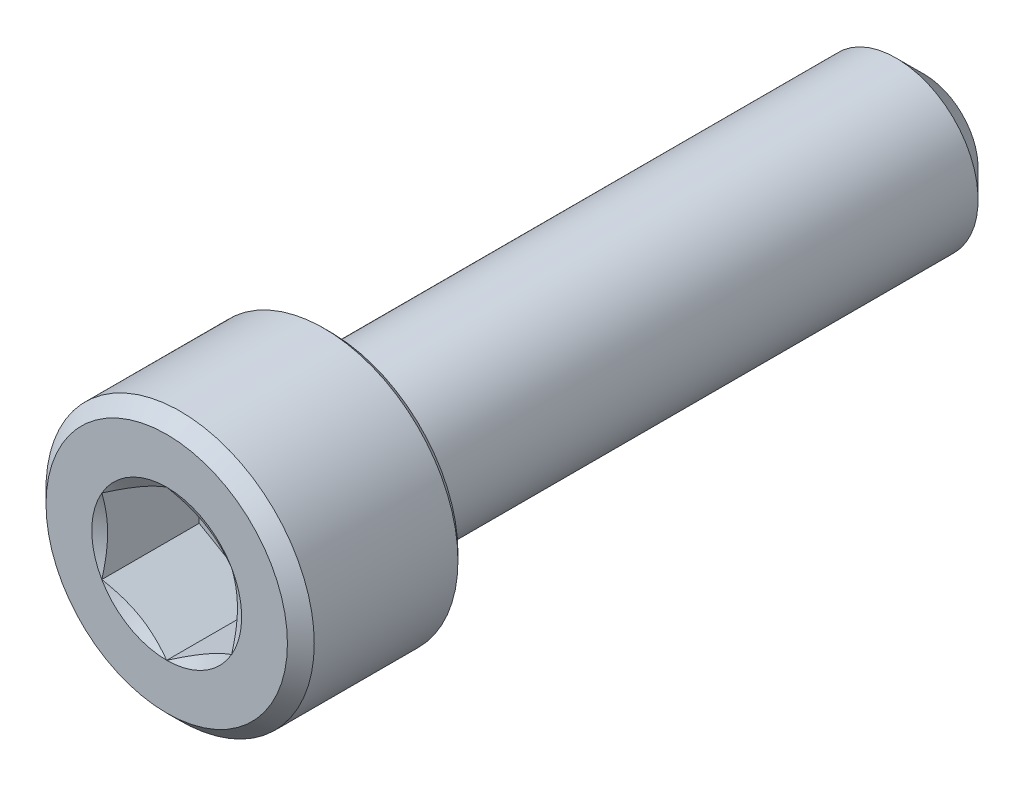
SolidWorks part; units mm, degrees
ref_plane "Front Plane" through (0, 0, 0) normal (0, 0, 1) x (1, 0, 0)
ref_plane "Top Plane" through (0, 0, 0) normal (0, 1, 0) x (1, 0, 0)
ref_plane "Right Plane" through (0, 0, 0) normal (1, 0, 0) x (0, 0, -1)
sketch "Sketch1" plane through (0, 0, 0) normal (1, 0, 0) x (0, 0, -1)
  line L0 (8.1026, 0) -> (-8.1026, 0) construction
  line L1 (-8.1026, 0) -> (-8.1026, 2.8702) construction
  line L2 (-4.5974, 1.7526) -> (-4.5974, 0) construction
  line L3 (7.3089, 0) -> (7.3089, 0.7938) construction
  line L4 (-4.5974, 0) -> (-4.5974, -1.7526) construction
  point P6 (-8.1026, 1.3891)
  point P9 (-8.1026, -1.3891)
  point P10 (-4.5974, 0)
  point P13 (5.3245, -1.7526)
  dimension "D1" = 0.7937
  dimension "D2" = 2.7781
sketch "Sketch2" plane through (0, 0, 0) normal (1, 0, 0) x (0, 0, -1)
  line L0 (8.1026, 1.1573) -> (7.5073, 1.7526)
  line L1 (-8.1026, 2.8702) -> (-4.5974, 2.8702)
  line L2 (-8.1026, 2.8702) -> (-8.1026, 0)
  line L4 (-4.5974, 2.8702) -> (-4.5974, 1.7526)
  line L5 (-4.5974, 1.7526) -> (7.5073, 1.7526)
  line L8 (8.1026, 1.1573) -> (8.1026, 0)
  line L9 (8.1026, 0) -> (-8.1026, 0) construction
  line L10 (8.1026, 0) -> (-8.1026, 0)
  dimension "D1" = 135
  dimension "D2" = 0.5953
revolve "Revolve1" add sketch "Sketch2" angle 360 about L10
sketch "Sketch4" plane through (0, 0, 8.1026) normal (0, 0, 1) x (1, 0, 0)
  line L1 (0, 1.604) -> (-1.3891, 0.802)
  line L2 (-1.3891, 0.802) -> (-1.3891, -0.802)
  line L3 (-1.3891, -0.802) -> (0, -1.604)
  line L4 (0, -1.604) -> (1.3891, -0.802)
  line L5 (1.3891, -0.802) -> (1.3891, 0.802)
  line L6 (1.3891, 0.802) -> (0, 1.604)
  circle A0 centre (0, 0) radius 1.3891 construction
  circle A1 centre (0, 0) radius 2.8702 construction
  circle A2 centre (0, 0) radius 2.8702 construction
  dimension "D1" = 2.7781
extrude "Cut-Extrude1" cut sketch "Sketch4" against normal blind 2.0836
sketch "Sketch5" plane through (0, 0, 8.1026) normal (0, 0, 1) x (1, 0, 0)
  circle A0 centre (0, 0) radius 1.604
extrude "Cut-Extrude2" cut sketch "Sketch5" against normal blind 10 draft 60
chamfer "Chamfer1" distance 0.287 angle 45 1 edges at (-2.8702, 0, 8.1026)
chamfer "Chamfer2" distance 0.1435 angle 45 1 edges at (-2.8702, 0, 4.5974)
sketch "Sketch3" [suppressed] plane through (0, 0, -8.1026) normal (0, 0, -1) x (-1, 0, 0)
  circle A0 centre (0, 0) radius 1.7526 construction
  circle A1 centre (0, 0) radius 1.7526
ref_axis "Center Axis1" through (0, 0, -5.7312) along (0, 0, 1)
ref_plane "Contact Plane1" through (0, 0, -8.1026) normal (0, 0, 1) x (1, 0, 0)
ref_plane "Contact Plane2" through (0, 0, 4.5974) normal (0, 0, 1) x (1, 0, 0)
split "Split1" [suppressed] bodies to split 106
curve "Helix/Spiral1" [suppressed] pitch 0.7937 height 13.4937 turns 17
sketch "Sketch7" [suppressed] plane through (0, 0, 0) normal (1, 0, 0) x (0, 0, -1)
  line L0 (8.053, 1.8385) -> (8.4499, 1.1511) construction
  line L1 (8.4499, 1.1511) -> (8.8467, 1.8385) construction
  line L2 (8.8467, 1.8385) -> (8.053, 1.8385) construction
  line L3 (8.1026, 1.7526) -> (8.7971, 1.7526)
  line L4 (8.4499, 1.8385) -> (8.4499, 1.7526) construction
  line L5 (8.4499, 1.7526) -> (8.4499, 1.237) construction
  line L6 (8.4499, 1.237) -> (8.4499, 1.1511) construction
  line L7 (8.4003, 1.237) -> (8.4995, 1.237)
  line L8 (8.0778, 1.7956) -> (8.8219, 1.7956) construction
  line L9 (8.4995, 1.237) -> (8.7971, 1.7526)
  line L10 (8.4003, 1.237) -> (8.1026, 1.7526)
  point P0 (8.4499, 1.7956)
  dimension "D1" = 0.7937
  dimension "D2" = 0.0992
sweep "Cut-Sweep1" [suppressed] cut profiles "Sketch7" path "Helix/Spiral1"
sketch "Sketch11" [suppressed] plane through (0, 0, 4.5974) normal (0, 0, -1) x (-1, 0, 0)
  circle A0 centre (0, 0) radius 1.7526
extrude "Boss-Extrude4" [suppressed] add sketch "Sketch11" along normal through all draft 45
sketch "Sketch9" [suppressed] plane through (0, 0, 4.5974) normal (0, 0, -1) x (-1, 0, 0)
  line L0 (0, 0) -> (0, 2.8702) construction
  line L1 (0, 2.7267) -> (-0.3008, 3.0137)
  line L2 (-0.3008, 3.0137) -> (0.3008, 3.0137)
  line L3 (0.3008, 3.0137) -> (0, 2.7267)
  line L4 (-0.1504, 2.8702) -> (0, 0) construction
  line L5 (0, 0) -> (0.1504, 2.8702) construction
  circle A0 centre (0, 0) radius 2.8702 construction
  circle A1 centre (0, 0) radius 2.7267 construction
  dimension "D1" = 0.287
  dimension "D2" = 6
extrude "Cut-Extrude3" [suppressed] cut sketch "Sketch9" against normal up to next
pattern_circular "CirPattern1" [suppressed] count 60 over 360 of bodies 112
equation "\"D1@Sketch1\"=\"Pitch@Sketch1\""
equation "\"D2@Sketch2\"=\"D1@Sketch1\"*.75"
equation "\"D4@Helix/Spiral1\"=\"Pitch@Sketch1\""
equation "\"D3@Helix/Spiral1\"=\"Length@Sketch1\"+\"Pitch@Sketch1\""
equation "\"D1@Sketch4\" = \"Drive Size@Sketch1\""
equation "\"D1@Cut-Extrude1\"=\"D1@Sketch4\"*.75"
equation "\"D19\"= \"D1@Sketch4\" * .75"
equation "\"D1@Chamfer1\" = \"Head Diameter@Sketch1\" * .05"
equation "\"D1@Chamfer2\"=\"D1@Chamfer1\"/2"
equation "\"D2@Sketch7\"=\"D1@Sketch7\"/8"
equation "\"D1@Sketch7\"=\"D4@Helix/Spiral1\""
equation "\"D2@Sketch1\"=\"Pitch@Sketch1\"*3.5"
equation "\"D1@Sketch9\"=\"D1@Chamfer1\""
equation "\"D1@CirPattern1\"=\"D3@CirPattern1\"/\"D2@Sketch9\""
